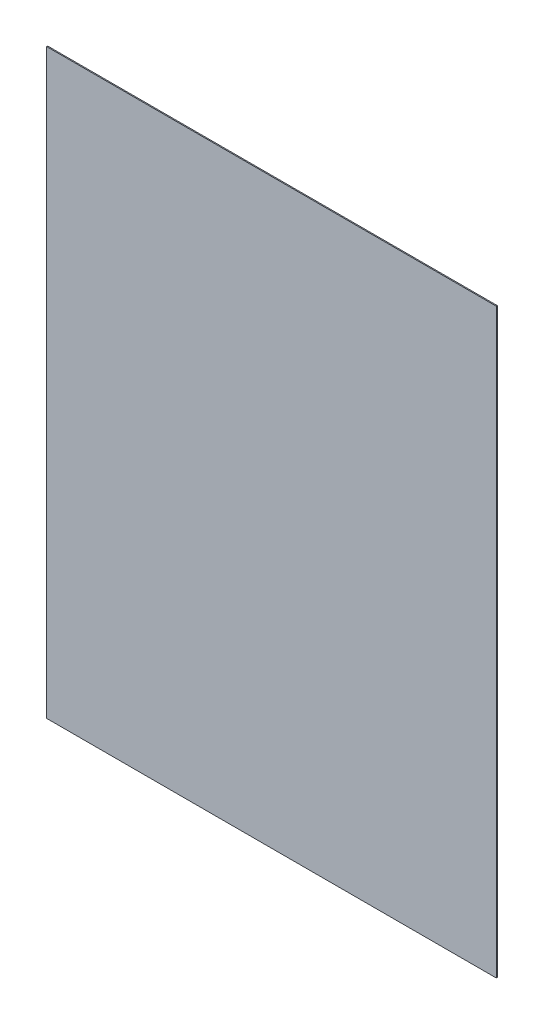
SolidWorks part; units mm, degrees
material "ABS PC"
ref_plane "Front Plane" through (0, 0, 0) normal (0, 0, 1) x (1, 0, 0)
ref_plane "Top Plane" through (0, 0, 0) normal (0, 1, 0) x (1, 0, 0)
ref_plane "Right Plane" through (0, 0, 0) normal (1, 0, 0) x (0, 0, -1)
sketch "Sketch1" plane through (0, 0, 0) normal (0, 0, 1) x (1, 0, 0)
  line L1 (-107.95, -139.7) -> (107.95, -139.7)
  line L2 (-107.95, -139.7) -> (-107.95, 139.7)
  line L3 (-107.95, 139.7) -> (107.95, 139.7)
  line L4 (107.95, -139.7) -> (107.95, 139.7)
  line L5 (-107.95, -139.7) -> (107.95, 139.7) construction
  line L6 (-107.95, 139.7) -> (107.95, -139.7) construction
  point P0 (0, 0)
  dimension "D1" = 215.9
  dimension "D2" = 279.4
extrude "Boss-Extrude1" add sketch "Sketch1" along normal blind 0.5
